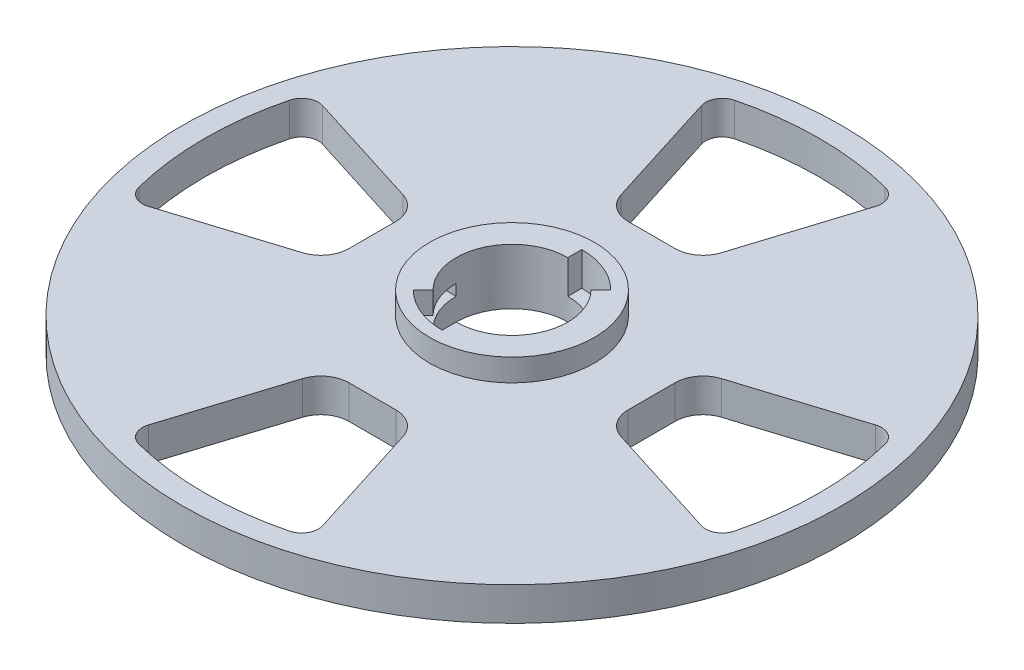
SolidWorks part; units mm, degrees
ref_plane "Front Plane" through (0, 0, 0) normal (0, 0, 1) x (1, 0, 0)
ref_plane "Top Plane" through (0, 0, 0) normal (0, 1, 0) x (1, 0, 0)
ref_plane "Right Plane" through (0, 0, 0) normal (1, 0, 0) x (0, 0, -1)
sketch "Sketch1" plane through (0, 0, 0) normal (0, 1, 0) x (1, 0, 0)
  circle A0 centre (0, 0) radius 59
  dimension "D1" = 118
extrude "Boss-Extrude1" add sketch "Sketch1" along normal blind 6
sketch "Sketch2" plane through (0, 6, 0) normal (0, 1, 0) x (1, 0, 0)
  line L0 (0, 0) -> (0, 55) construction
  line L1 (3.6084, -6.25) -> (7.2169, 0)
  line L2 (7.2169, 0) -> (3.6084, 6.25)
  line L3 (3.6084, 6.25) -> (-3.6084, 6.25)
  line L4 (-3.6084, 6.25) -> (-7.2169, 0)
  line L5 (-7.2169, 0) -> (-3.6084, -6.25)
  line L6 (-3.6084, -6.25) -> (3.6084, -6.25)
  line L7 (0, 0) -> (-9.0212, 28.6115) construction
  line L8 (0, 0) -> (1.9706, 6.25) construction
  line L9 (-8.9849, 28.4965) -> (-15.6107, 49.5107)
  line L10 (8.9849, 28.4965) -> (15.6107, 49.5107)
  line L11 (-4.2163, 25) -> (4.2163, 25)
  circle A0 centre (0, 0) radius 6.25 construction
  arc A2 (13.4851, 53.3212) -> (-13.4851, 53.3212) centre (0, 0) ccw
  arc A4 (13.4851, 53.3212) -> (15.6107, 49.5107) centre (12.7495, 50.4128) cw
  arc A5 (-13.4851, 53.3212) -> (-15.6107, 49.5107) centre (-12.7495, 50.4128) ccw
  arc A8 (8.9849, 28.4965) -> (4.2163, 25) centre (4.2163, 30) cw
  arc A9 (-4.2163, 25) -> (-8.9849, 28.4965) centre (-4.2163, 30) cw
  dimension "D2" = 110
  dimension "D3" = 25
  dimension "D5" = 5
  dimension "D6" = 3
  dimension "D1" = 12.5
  dimension "D4" = 35
extrude "Cut-Extrude3" [suppressed] cut sketch "Sketch2" against normal through all contours L5 L6 L1 L2 L3 L4
extrude "Cut-Extrude4" cut sketch "Sketch2<3>" against normal through all contours A2 A5 L9 L10 A4 region at (0, 6, -41.4144)
sketch "Sketch2<3>" plane through (0, 6, 0) normal (0, 1, 0) x (1, 0, 0) same geometry as "Sketch2"
pattern_circular "CirPattern2" count 4 over 360 about axis through (0, 6, 0) along (0, -1, 0) of "Cut-Extrude4" reverse direction yes
sketch "Sketch4" plane through (0, 6, 0) normal (0, 1, 0) x (1, 0, 0)
  circle A0 centre (0, 0) radius 10
  dimension "D1" = 20
extrude "Cut-Extrude6" cut sketch "Sketch4" against normal blind 10
sketch "Sketch5" plane through (0, 6, 0) normal (0, 1, 0) x (1, 0, 0)
  circle A0 centre (0, 0) radius 10 construction
  circle A1 centre (0, 0) radius 10
  circle A2 centre (0, 0) radius 14.75
  dimension "D1" = 29.5
extrude "Boss-Extrude2" add sketch "Sketch5" along normal blind 4
sketch "Sketch6" plane through (0, 10, 0) normal (0, 1, 0) x (1, 0, 0)
  line L0 (0, 0) -> (0, 12.5)
  line L1 (0, 0) -> (8.8388, 8.8388)
  line L2 (0, 0) -> (12.5, 0)
  circle A0 centre (0, 0) radius 10 construction
  circle A1 centre (0, 0) radius 10
  circle A2 centre (0, 0) radius 12.5
  circle M5 centre (0, 0) radius 10
  dimension "D1" = 2.5
  dimension "D2" = 45
extrude "Cut-Extrude8" cut sketch "Sketch6" against normal blind 6 contours L1 A2 L0 M5 region at (4.2127, 10, -10.1702)
extrude "Cut-Extrude9" cut sketch "Sketch6<4>" against normal blind 2 from offset 4 contours L2 A2 L1 M5 region at (10.1702, 10, -4.2127) offset against normal yes
sketch "Sketch6<4>" plane through (0, 10, 0) normal (0, 1, 0) x (1, 0, 0) same geometry as "Sketch6"
pattern_circular "CirPattern3" count 2 over 360 about axis through (0, -4, 0) along (0, 1, 0) of "Cut-Extrude8", "Cut-Extrude9" reverse direction yes
equation "\"29.5.E4\"=38.9006"
